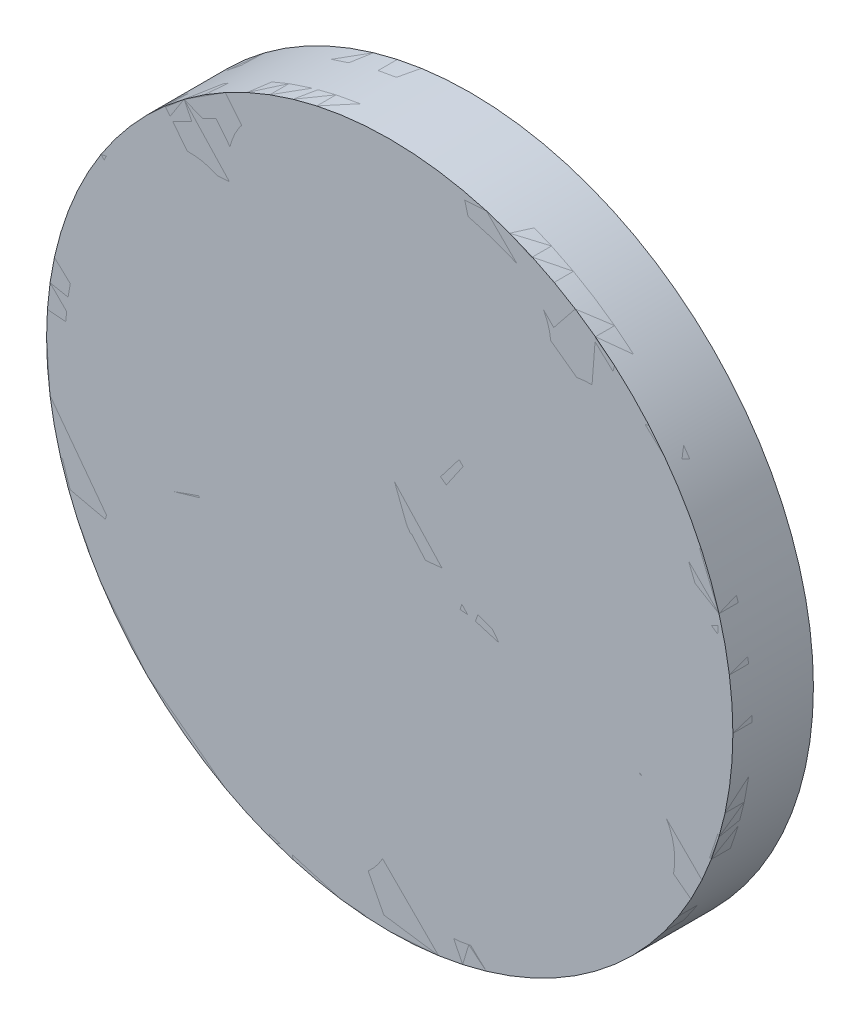
SolidWorks part; units mm, degrees
ref_plane "Front" through (0, 0, 0) normal (0, 0, 1) x (1, 0, 0)
ref_plane "Top" through (0, 0, 0) normal (0, 1, 0) x (1, 0, 0)
ref_plane "Right" through (0, 0, 0) normal (1, 0, 0) x (0, 0, -1)
sketch "Sketch1" plane through (0, 0, 0) normal (0, 0, 1) x (1, 0, 0)
  line L0 (-2.0151, 6.4362) -> (-8.7724, 15.2424)
  line L1 (2.0151, 6.4362) -> (8.7724, 15.2424)
  circle A0 centre (0, 0) radius 23.8125
  arc A1 (-7.7057, 19.145) -> (7.7057, 19.145) centre (0, 0) cw
  arc A2 (-2.0151, 6.4362) -> (2.0151, 6.4362) centre (0, 7.9824) ccw
  arc A3 (8.7724, 15.2424) -> (7.7057, 19.145) centre (6.7573, 16.7887) ccw
  arc A4 (-8.7724, 15.2424) -> (-7.7057, 19.145) centre (-6.7573, 16.7887) cw
  point P8 (0, 3.81)
  dimension "D1" = 47.625
  dimension "D2" = 3.175
  dimension "D4" = 2.54
  dimension "D5" = 75
  dimension "D3" = 3.81
extrude "Boss-Extrude1" add sketch "Sketch1" along normal mid plane 5.588 contours A0
sketch "Sketch2" plane through (0, 0, 2.794) normal (0, 0, 1) x (1, 0, 0)
  line L0 (-1.1979, 1.1438) -> (1.1979, 1.1438)
  line L1 (0, 1.1438) -> (0, -1.6562) construction
  arc A0 (-1.1979, 1.1438) -> (1.1979, 1.1438) centre (0, 0) ccw
  dimension "D1" = 3.3125
  dimension "D2" = 2.8
sketch "Sketch3" plane through (0, 0, 0) normal (1, 0, 0) x (0, 0, -1)
  line L0 (2.794, 23.8125) -> (-2.794, 23.8125) construction
  line L1 (-1.5875, 23.8125) -> (-1.5875, 26.3525) construction
  line L2 (-1.5875, 26.3525) -> (1.5875, 26.3525) construction
  line L3 (1.5875, 26.3525) -> (1.5875, 23.8125) construction
  line L4 (1.4605, 26.2255) -> (1.4605, 23.8125)
  line L5 (-1.4605, 26.2255) -> (1.4605, 26.2255)
  line L6 (-1.4605, 23.8125) -> (-1.4605, 26.2255)
  arc A0 (-1.5875, 23.8125) -> (1.5875, 23.8125) centre (0, 23.8125) ccw construction
  arc A1 (-1.4605, 23.8125) -> (1.4605, 23.8125) centre (0, 23.8125) ccw
  dimension "D1" = 1.5875
  dimension "D2" = 2.54
  dimension "D3" = 0.127
extrude "Boss-Extrude2" add sketch "Sketch1<4>" along normal mid plane 5.588 separate body contours A0
sketch "Sketch1<4>" plane through (0, 0, 0) normal (0, 0, 1) x (1, 0, 0) same geometry as "Sketch1"
extrude "Cut-Extrude3" cut sketch "Sketch1<5>" against normal through all both and the other way through all contours L0 A4 A1 A3 L1 A2
sketch "Sketch1<5>" plane through (0, 0, 0) normal (0, 0, 1) x (1, 0, 0) same geometry as "Sketch1"
pattern_circular "CirPattern2" count 5 over 360 about axis through (0, 0, 2.794) along (0, 0, 1) of "Cut-Extrude3"
fillet "Fillet2" radius 1.905 60 edges at (5.3938, 10.8393, 2.794) (9.2074, 17.4584, 2.794) (0, 20.6375, 2.794) (-9.2074, 17.4584, 2.794) (-5.3938, 10.8393, 2.794) (0, 5.4424, 2.794) (-8.642, 8.4793, 2.794) (-13.7587, 14.1517, 2.794) (-19.6274, 6.3773, 2.794) (-19.4491, -3.3618, 2.794) (-11.9755, -1.7802, 2.794) (-5.176, 1.6818, 2.794) (3.199, -4.403, -2.794) (2.0075, -11.9395, -2.794) (2.8128, -19.5361, -2.794) (12.1304, -16.6961, -2.794) (17.7107, -8.7122, -2.794) (-3.199, -4.403, -2.794) (-10.7348, -5.5988, -2.794) (-17.7107, -8.7122, -2.794) (-12.1304, -16.6961, -2.794) (-2.8128, -19.5361, -2.794) (-5.176, 1.6818, -2.794) (-11.9755, -1.7802, -2.794) (-19.4491, -3.3618, -2.794) (-19.6274, 6.3773, -2.794) (-13.7587, 14.1517, -2.794) (0, 5.4424, -2.794) (-5.3938, 10.8393, -2.794) (-9.2074, 17.4584, -2.794) (0, 20.6375, -2.794) (9.2074, 17.4584, -2.794) (5.176, 1.6818, 2.794) (11.9755, -1.7802, 2.794) (19.4491, -3.3618, 2.794) (19.6274, 6.3773, 2.794) (13.7587, 14.1517, 2.794) (-3.199, -4.403, 2.794) (-10.7348, -5.5988, 2.794) (-17.7107, -8.7122, 2.794) (-12.1304, -16.6961, 2.794) (-2.8128, -19.5361, 2.794) (3.199, -4.403, 2.794) (2.0075, -11.9395, 2.794) (2.8128, -19.5361, 2.794) (12.1304, -16.6961, 2.794) (17.7107, -8.7122, 2.794) (5.176, 1.6818, -2.794) (11.9755, -1.7802, -2.794) (19.4491, -3.3618, -2.794) (19.6274, 6.3773, -2.794) (13.7587, 14.1517, -2.794) (10.7348, -5.5988, -2.794) (-2.0075, -11.9395, -2.794) (-8.642, 8.4793, -2.794) (5.3938, 10.8393, -2.794) (8.642, 8.4793, 2.794) (-2.0075, -11.9395, 2.794) (10.7348, -5.5988, 2.794) (8.642, 8.4793, -2.794)
extrude "Cut-Extrude4" cut sketch "Sketch2" against normal through all both and the other way through all
sketch "Sketch7" plane through (0, 0, 0) normal (0, 0, 1) x (1, 0, 0)
  circle A0 centre (0, 0) radius 23.8125
sweep "Cut-Sweep2" cut profiles "Sketch3" path "Sketch7"
